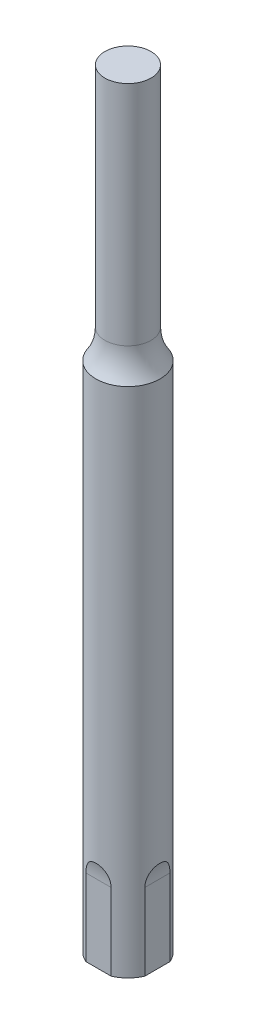
SolidWorks part; units mm, degrees
ref_plane "Front Plane" through (0, 0, 0) normal (0, 0, 1) x (1, 0, 0)
ref_plane "Top Plane" through (0, 0, 0) normal (0, 1, 0) x (1, 0, 0)
ref_plane "Right Plane" through (0, 0, 0) normal (1, 0, 0) x (0, 0, -1)
sketch "Sketch1" plane through (0, 0, 0) normal (0, 1, 0) x (1, 0, 0)
  circle A0 centre (0, 0) radius 6.35
  dimension "D1" = 12.7
extrude "Boss-Extrude1" add sketch "Sketch1" along normal blind 25.4
sketch "Sketch3" plane through (0, 0, 0) normal (0, -1, 0) x (1, 0, 0)
  line L9 (5.842, -5.5965) -> (9.6049, -5.5965)
  line L10 (9.6049, -5.5965) -> (9.6049, 5.5768)
  line L11 (9.6049, 5.5768) -> (5.842, 5.5768)
  line L15 (-5.842, 5.5768) -> (-5.842, -5.5965)
  line L16 (-10.0312, -5.5965) -> (-10.0312, 5.5768)
  line L17 (-10.0312, 5.5768) -> (-5.842, 5.5768)
  line L18 (-10.0312, -5.5965) -> (-5.842, -5.5965)
  line L20 (5.842, -5.5965) -> (5.842, 5.5768)
  circle A0 centre (0, 0) radius 6.35 construction
  dimension "D1" = 5.842
  dimension "D2" = 5.5768
  dimension "D3" = 9.6049
  dimension "D4" = 10.0312
  dimension "D5" = 5.842
  dimension "D6" = 5.5965
extrude "Cut-Extrude2" cut sketch "Sketch3" against normal blind 25.4
sketch "Sketch4" plane through (0, 0, 0) normal (0, -1, 0) x (1, 0, 0)
  line L4 (0, 0) -> (3.9441, 0) construction
  line L10 (0, 0) -> (0, -5.842) construction
  line L18 (5.524, -5.842) -> (-7.0598, -5.842)
  line L19 (-7.0598, -5.842) -> (-7.0598, -10.8724)
  line L20 (-7.0598, -10.8724) -> (5.524, -11.067)
  line L21 (5.524, -11.067) -> (5.524, -5.842)
  line L22 (5.842, -2.4887) -> (5.842, 2.4887) construction
  dimension "D1" = 5.842
  dimension "D2" = 0.318
  dimension "D3" = 12.9018
  dimension "D4" = 13.361
  dimension "D5" = 13.5556
extrude "Cut-Extrude3" cut sketch "Sketch4" against normal blind 25.4
sketch "Sketch5" plane through (0, 25.4, 0) normal (0, 1, 0) x (1, 0, 0)
  circle A0 centre (0, 0) radius 6.35
  dimension "D1" = 12.7
extrude "Boss-Extrude2" add sketch "Sketch5" along normal blind 76.2
fillet "Fillet2" radius 10.16 2 edges at (-5.842, 25.4, 0) (5.842, 25.4, 0)
mirror "Mirror1" about plane through (0, 0, 0) normal (0, 0, 1) of "Cut-Extrude3"
fillet "Fillet3" radius 10.16 2 edges at (0, 25.4, 5.842) (0, 25.4, -5.842)
sketch "Sketch6" plane through (0, 101.6, 0) normal (0, 1, 0) x (1, 0, 0)
  circle A0 centre (0, 0) radius 4.572
  dimension "D1" = 9.144
extrude "Boss-Extrude3" add sketch "Sketch6" along normal blind 50.8
fillet "Fillet5" radius 10.16 1 edges at (0, 101.6, 4.572)
